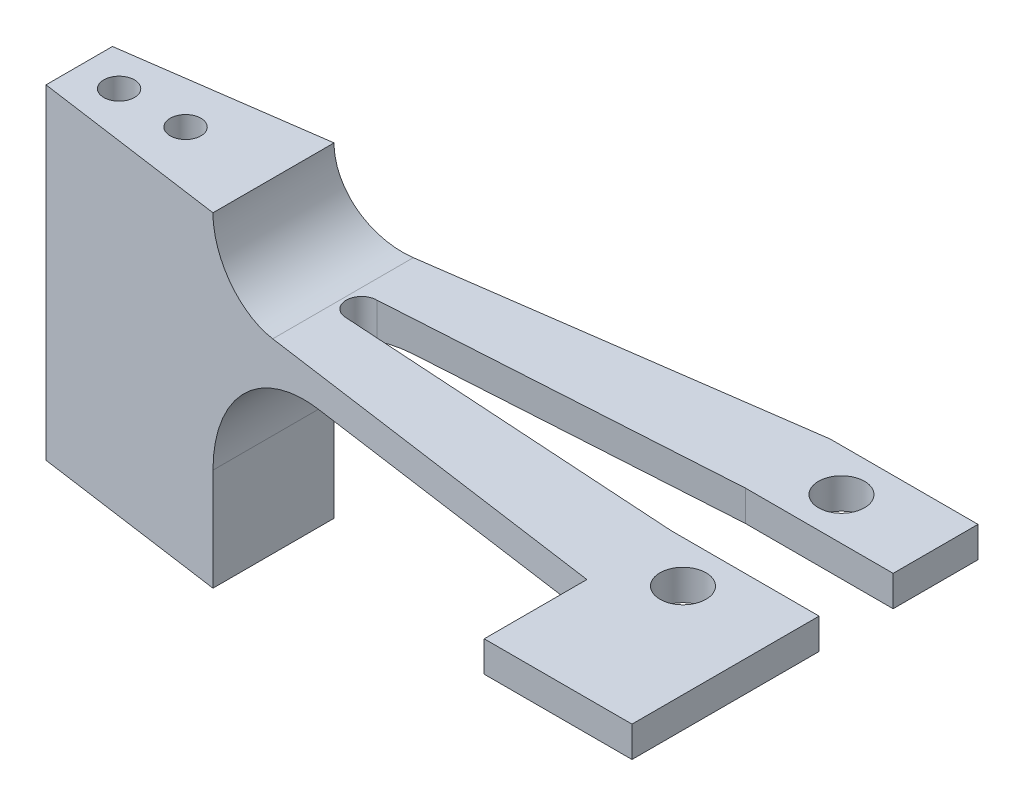
SolidWorks part; units mm, degrees
ref_plane "Front Plane" through (0, 0, 0) normal (0, 0, 1) x (1, 0, 0)
ref_plane "Top Plane" through (0, 0, 0) normal (0, 1, 0) x (1, 0, 0)
ref_plane "Right Plane" through (0, 0, 0) normal (1, 0, 0) x (0, 0, -1)
sketch "Sketch1" plane through (0, 0, 0) normal (0, 1, 0) x (1, 0, 0)
  line L0 (56.4, 7.75) -> (56.4, -7.75) construction
  line L1 (0, 0) -> (56.4, 0) construction
  line L2 (51.1479, 11.9) -> (65.6, 11.9)
  line L3 (65.6, 11.9) -> (65.6, 3.6)
  line L4 (65.6, 3.6) -> (51.1479, 3.6)
  line L8 (51.1479, -21.94) -> (65.6, -21.94)
  line L9 (65.6, -21.94) -> (65.6, -3.64)
  line L10 (65.6, -3.64) -> (51.1479, -3.64)
  line L11 (51.1479, -21.94) -> (51.1479, -11.9)
  line L13 (-10.4, -3.25) -> (-10.4, 3.25)
  line L14 (-10.4, 3.25) -> (51.1479, 11.9)
  line L15 (56.4, 7.75) -> (65.6, 7.75) construction
  line L16 (-10.4, 0) -> (-6.5, 0) construction
  line L17 (-10.4, -3.25) -> (51.1479, -11.9)
  line L18 (51.1479, 3.6) -> (17.2129, 1.5)
  line L19 (51.1479, -3.64) -> (17.2129, -1.5)
  circle A0 centre (-6.5, 0) radius 1.5
  circle A1 centre (0, 0) radius 1.5
  circle A2 centre (56.4, 7.75) radius 2.25
  circle A3 centre (56.4, -7.75) radius 2.25
  circle A5 centre (17.2129, 0) radius 1.5
  dimension "D4" = 3
  dimension "D5" = 4.5
  dimension "D14" = 3
  dimension "D1" = 6.5
  dimension "D2" = 56.4
  dimension "D3" = 15.5
  dimension "D6" = 8.3
  dimension "D7" = 98
  dimension "D8" = 98
  dimension "D9" = 9.2
  dimension "D10" = 76
  dimension "D11" = 18.3
  dimension "D12" = 7.24
  dimension "D13" = 6.5
  dimension "D15" = 34
extrude "Boss-Extrude1" add sketch "Sketch1" along normal blind 31.8 contours A5 L18 L4 L3 L2 L14 L13 L17 L11 L8 L9 L10 L19 A3 A2 A1 A0 | A1 | A0 region at (58.374, 0, -11.0681) region at (-6.5, 0, 0) region at (0, 0, 0)
sketch "Sketch2" plane through (0, 0, 0) normal (0, 0, 1) x (1, 0, 0)
  line L0 (-10.4, 31.8) -> (51.1479, 31.8) construction
  line L1 (15.4, 25) -> (65.6, 25)
  line L2 (65.6, 31.8) -> (65.6, 0) construction
  line L3 (65.6, 25) -> (65.6, 31.8)
  line L4 (65.6, 31.8) -> (8.6, 31.8)
  line L5 (-10.4, 31.8) -> (-10.4, 0) construction
  line L6 (65.6, 22) -> (20.6, 22)
  line L7 (8.6, 10) -> (8.6, 0)
  line L8 (-10.4, 0) -> (51.1479, 0) construction
  line L9 (8.6, 0) -> (65.6, 0)
  line L10 (65.6, 0) -> (65.6, 22)
  arc A0 (8.6, 31.8) -> (15.4, 25) centre (15.4, 31.8) ccw
  arc A1 (20.6, 22) -> (8.6, 10) centre (20.6, 10) ccw
  point P16 (0, 0)
  point P22 (20.4485, 10.1515)
  dimension "D4" = 12
  dimension "D1" = 6.8
  dimension "D2" = 19
  dimension "D3" = 3
extrude "Cut-Extrude1" cut sketch "Sketch2" against normal through all both and the other way through all
extrude "Cut-Extrude2" cut sketch "Sketch1<3>" against normal blind 5.6 from surface contours A1 | A0 region at (0, 0, 0) starting at face at (-0.9, 31.8, 0)
sketch "Sketch1<3>" plane through (0, 0, 0) normal (0, 1, 0) x (1, 0, 0) same geometry as "Sketch1"
equation "\"D8@Sketch1\"=\"D7@Sketch1\""
